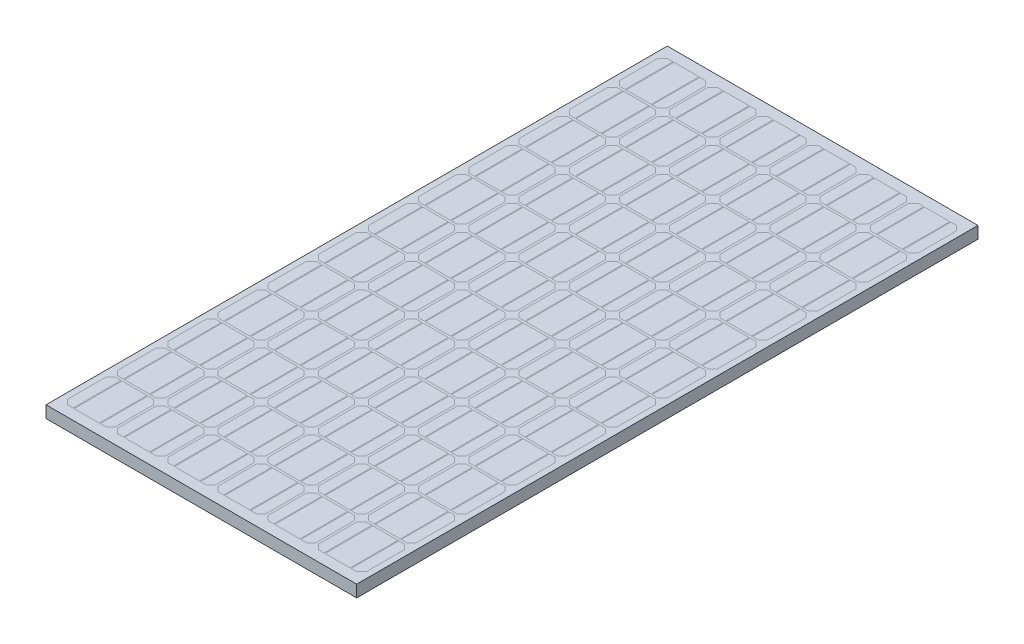
SolidWorks part; units mm, degrees
ref_plane "Front Plane" through (0, 0, 0) normal (0, 0, 1) x (1, 0, 0)
ref_plane "Top Plane" through (0, 0, 0) normal (0, 1, 0) x (1, 0, 0)
ref_plane "Right Plane" through (0, 0, 0) normal (1, 0, 0) x (0, 0, -1)
sketch "Sketch1" plane through (0, 0, 0) normal (0, 1, 0) x (1, 0, 0)
  line L1 (495.3, -990.6) -> (-495.3, -990.6)
  line L2 (495.3, -990.6) -> (495.3, 990.6)
  line L3 (495.3, 990.6) -> (-495.3, 990.6)
  line L4 (-495.3, -990.6) -> (-495.3, 990.6)
  line L5 (495.3, -990.6) -> (-495.3, 990.6) construction
  line L6 (495.3, 990.6) -> (-495.3, -990.6) construction
  point P0 (0, 0)
  dimension "D1" = 1981.2
  dimension "D2" = 990.6
extrude "Boss-Extrude1" add sketch "Sketch1" along normal blind 38.1
sketch "Sketch2" plane through (0, 38.1, 0) normal (0, 1, 0) x (1, 0, 0)
  line L0 (-495.3, 990.6) -> (-495.3, -990.6) construction
  line L1 (-461.2, 956.2) -> (-443, 956.2)
  line L2 (-476.2, 941.2) -> (-476.2, 818.8)
  line L3 (-461.2, 803.8) -> (-443, 803.8)
  line L4 (-323.8, 941.2) -> (-323.8, 818.8)
  line L5 (-476.2, 956.2) -> (-323.8, 803.8) construction
  line L6 (-476.2, 803.8) -> (-323.8, 956.2) construction
  line L7 (495.3, 990.6) -> (-495.3, 990.6) construction
  line L8 (-476.2, 941.2) -> (-461.2, 956.2)
  line L9 (-338.8, 956.2) -> (-323.8, 941.2)
  line L10 (-476.2, 818.8) -> (-461.2, 803.8)
  line L11 (-338.8, 803.8) -> (-323.8, 818.8)
  line L20 (-301.2, 956.2) -> (-283, 956.2)
  line L21 (-316.2, 941.2) -> (-316.2, 818.8)
  line L30 (-301.2, 803.8) -> (-283, 803.8)
  line L31 (-163.8, 941.2) -> (-163.8, 818.8)
  line L40 (-316.2, 941.2) -> (-301.2, 956.2)
  line L41 (-178.8, 956.2) -> (-163.8, 941.2)
  line L50 (-316.2, 818.8) -> (-301.2, 803.8)
  line L51 (-178.8, 803.8) -> (-163.8, 818.8)
  line L60 (-283, 956.2) -> (-283, 803.8)
  line L61 (-280, 956.2) -> (-280, 803.8)
  line L110 (-200, 956.2) -> (-200, 803.8)
  line L111 (-197, 956.2) -> (-197, 803.8)
  line L112 (-280, 956.2) -> (-200, 956.2)
  line L113 (-197, 956.2) -> (-178.8, 956.2)
  line L114 (-280, 803.8) -> (-200, 803.8)
  line L115 (-197, 803.8) -> (-178.8, 803.8)
  line L116 (-316.2, 956.2) -> (-163.8, 803.8) construction
  line L117 (-316.2, 803.8) -> (-163.8, 956.2) construction
  line L118 (-240, 956.2) -> (-240, 803.8) construction
  line L119 (-141.2, 956.2) -> (-123, 956.2)
  line L120 (-156.2, 941.2) -> (-156.2, 818.8)
  line L121 (-141.2, 803.8) -> (-123, 803.8)
  line L170 (-3.8, 941.2) -> (-3.8, 818.8)
  line L171 (-156.2, 941.2) -> (-141.2, 956.2)
  line L172 (-18.8, 956.2) -> (-3.8, 941.2)
  line L173 (-156.2, 818.8) -> (-141.2, 803.8)
  line L174 (-18.8, 803.8) -> (-3.8, 818.8)
  line L175 (-123, 956.2) -> (-123, 803.8)
  line L176 (-120, 956.2) -> (-120, 803.8)
  line L177 (-40, 956.2) -> (-40, 803.8)
  line L178 (-37, 956.2) -> (-37, 803.8)
  line L179 (-120, 956.2) -> (-40, 956.2)
  line L180 (-37, 956.2) -> (-18.8, 956.2)
  line L181 (-120, 803.8) -> (-40, 803.8)
  line L230 (-37, 803.8) -> (-18.8, 803.8)
  line L231 (-156.2, 956.2) -> (-3.8, 803.8) construction
  line L232 (-156.2, 803.8) -> (-3.8, 956.2) construction
  line L233 (-80, 956.2) -> (-80, 803.8) construction
  line L234 (18.8, 956.2) -> (37, 956.2)
  line L235 (3.8, 941.2) -> (3.8, 818.8)
  line L236 (18.8, 803.8) -> (37, 803.8)
  line L237 (156.2, 941.2) -> (156.2, 818.8)
  line L238 (3.8, 941.2) -> (18.8, 956.2)
  line L239 (141.2, 956.2) -> (156.2, 941.2)
  line L240 (3.8, 818.8) -> (18.8, 803.8)
  line L241 (141.2, 803.8) -> (156.2, 818.8)
  line L290 (37, 956.2) -> (37, 803.8)
  line L291 (40, 956.2) -> (40, 803.8)
  line L292 (120, 956.2) -> (120, 803.8)
  line L293 (123, 956.2) -> (123, 803.8)
  line L294 (40, 956.2) -> (120, 956.2)
  line L295 (123, 956.2) -> (141.2, 956.2)
  line L296 (40, 803.8) -> (120, 803.8)
  line L297 (123, 803.8) -> (141.2, 803.8)
  line L298 (3.8, 956.2) -> (156.2, 803.8) construction
  line L299 (3.8, 803.8) -> (156.2, 956.2) construction
  line L300 (80, 956.2) -> (80, 803.8) construction
  line L301 (178.8, 956.2) -> (197, 956.2)
  line L350 (163.8, 941.2) -> (163.8, 818.8)
  line L351 (178.8, 803.8) -> (197, 803.8)
  line L352 (316.2, 941.2) -> (316.2, 818.8)
  line L353 (163.8, 941.2) -> (178.8, 956.2)
  line L354 (301.2, 956.2) -> (316.2, 941.2)
  line L355 (163.8, 818.8) -> (178.8, 803.8)
  line L356 (301.2, 803.8) -> (316.2, 818.8)
  line L357 (197, 956.2) -> (197, 803.8)
  line L358 (200, 956.2) -> (200, 803.8)
  line L359 (280, 956.2) -> (280, 803.8)
  line L360 (283, 956.2) -> (283, 803.8)
  line L361 (200, 956.2) -> (280, 956.2)
  line L410 (283, 956.2) -> (301.2, 956.2)
  line L411 (200, 803.8) -> (280, 803.8)
  line L412 (283, 803.8) -> (301.2, 803.8)
  line L413 (163.8, 956.2) -> (316.2, 803.8) construction
  line L414 (163.8, 803.8) -> (316.2, 956.2) construction
  line L415 (240, 956.2) -> (240, 803.8) construction
  line L416 (338.8, 956.2) -> (357, 956.2)
  line L417 (323.8, 941.2) -> (323.8, 818.8)
  line L418 (338.8, 803.8) -> (357, 803.8)
  line L419 (476.2, 941.2) -> (476.2, 818.8)
  line L420 (323.8, 941.2) -> (338.8, 956.2)
  line L421 (461.2, 956.2) -> (476.2, 941.2)
  line L470 (323.8, 818.8) -> (338.8, 803.8)
  line L471 (461.2, 803.8) -> (476.2, 818.8)
  line L472 (357, 956.2) -> (357, 803.8)
  line L473 (360, 956.2) -> (360, 803.8)
  line L474 (440, 956.2) -> (440, 803.8)
  line L475 (443, 956.2) -> (443, 803.8)
  line L476 (360, 956.2) -> (440, 956.2)
  line L477 (443, 956.2) -> (461.2, 956.2)
  line L478 (360, 803.8) -> (440, 803.8)
  line L479 (443, 803.8) -> (461.2, 803.8)
  line L480 (323.8, 956.2) -> (476.2, 803.8) construction
  line L481 (323.8, 803.8) -> (476.2, 956.2) construction
  line L530 (400, 956.2) -> (400, 803.8) construction
  line L531 (-461.2, 796.2) -> (-443, 796.2)
  line L532 (-476.2, 781.2) -> (-476.2, 658.8)
  line L533 (-461.2, 643.8) -> (-443, 643.8)
  line L534 (-323.8, 781.2) -> (-323.8, 658.8)
  line L535 (-476.2, 781.2) -> (-461.2, 796.2)
  line L536 (-338.8, 796.2) -> (-323.8, 781.2)
  line L537 (-476.2, 658.8) -> (-461.2, 643.8)
  line L538 (-338.8, 643.8) -> (-323.8, 658.8)
  line L539 (-301.2, 796.2) -> (-283, 796.2)
  line L540 (-316.2, 781.2) -> (-316.2, 658.8)
  line L541 (-301.2, 643.8) -> (-283, 643.8)
  line L590 (-163.8, 781.2) -> (-163.8, 658.8)
  line L591 (-316.2, 781.2) -> (-301.2, 796.2)
  line L592 (-178.8, 796.2) -> (-163.8, 781.2)
  line L593 (-316.2, 658.8) -> (-301.2, 643.8)
  line L594 (-178.8, 643.8) -> (-163.8, 658.8)
  line L595 (-283, 796.2) -> (-283, 643.8)
  line L596 (-280, 796.2) -> (-280, 643.8)
  line L597 (-200, 796.2) -> (-200, 643.8)
  line L598 (-197, 796.2) -> (-197, 643.8)
  line L599 (-280, 796.2) -> (-200, 796.2)
  line L600 (-197, 796.2) -> (-178.8, 796.2)
  line L601 (-280, 643.8) -> (-200, 643.8)
  line L650 (-197, 643.8) -> (-178.8, 643.8)
  line L651 (-141.2, 796.2) -> (-123, 796.2)
  line L652 (-156.2, 781.2) -> (-156.2, 658.8)
  line L653 (-141.2, 643.8) -> (-123, 643.8)
  line L654 (-3.8, 781.2) -> (-3.8, 658.8)
  line L655 (-156.2, 781.2) -> (-141.2, 796.2)
  line L656 (-18.8, 796.2) -> (-3.8, 781.2)
  line L657 (-156.2, 658.8) -> (-141.2, 643.8)
  line L658 (-18.8, 643.8) -> (-3.8, 658.8)
  line L659 (-123, 796.2) -> (-123, 643.8)
  line L660 (-120, 796.2) -> (-120, 643.8)
  line L661 (-40, 796.2) -> (-40, 643.8)
  line L710 (-37, 796.2) -> (-37, 643.8)
  line L711 (-120, 796.2) -> (-40, 796.2)
  line L712 (-37, 796.2) -> (-18.8, 796.2)
  line L713 (-120, 643.8) -> (-40, 643.8)
  line L714 (-37, 643.8) -> (-18.8, 643.8)
  line L715 (18.8, 796.2) -> (37, 796.2)
  line L716 (3.8, 781.2) -> (3.8, 658.8)
  line L717 (18.8, 643.8) -> (37, 643.8)
  line L718 (156.2, 781.2) -> (156.2, 658.8)
  line L719 (3.8, 781.2) -> (18.8, 796.2)
  line L720 (141.2, 796.2) -> (156.2, 781.2)
  line L721 (3.8, 658.8) -> (18.8, 643.8)
  line L722 (-400, 956.2) -> (-400, 803.8) construction
  line L724 (-443, 956.2) -> (-443, 803.8)
  line L726 (-440, 956.2) -> (-440, 803.8)
  line L727 (-360, 956.2) -> (-360, 803.8)
  line L728 (-357, 956.2) -> (-357, 803.8)
  line L729 (-440, 956.2) -> (-360, 956.2)
  line L730 (-357, 956.2) -> (-338.8, 956.2)
  line L731 (-440, 803.8) -> (-360, 803.8)
  line L732 (-357, 803.8) -> (-338.8, 803.8)
  line L733 (141.2, 643.8) -> (156.2, 658.8)
  line L734 (37, 796.2) -> (37, 643.8)
  line L735 (40, 796.2) -> (40, 643.8)
  line L736 (120, 796.2) -> (120, 643.8)
  line L737 (123, 796.2) -> (123, 643.8)
  line L738 (40, 796.2) -> (120, 796.2)
  line L739 (123, 796.2) -> (141.2, 796.2)
  line L740 (40, 643.8) -> (120, 643.8)
  line L741 (123, 643.8) -> (141.2, 643.8)
  line L742 (178.8, 796.2) -> (197, 796.2)
  line L743 (163.8, 781.2) -> (163.8, 658.8)
  line L744 (178.8, 643.8) -> (197, 643.8)
  line L745 (316.2, 781.2) -> (316.2, 658.8)
  line L746 (163.8, 781.2) -> (178.8, 796.2)
  line L747 (301.2, 796.2) -> (316.2, 781.2)
  line L748 (163.8, 658.8) -> (178.8, 643.8)
  line L749 (301.2, 643.8) -> (316.2, 658.8)
  line L750 (197, 796.2) -> (197, 643.8)
  line L751 (200, 796.2) -> (200, 643.8)
  line L752 (280, 796.2) -> (280, 643.8)
  line L753 (283, 796.2) -> (283, 643.8)
  line L754 (200, 796.2) -> (280, 796.2)
  line L755 (283, 796.2) -> (301.2, 796.2)
  line L756 (200, 643.8) -> (280, 643.8)
  line L757 (283, 643.8) -> (301.2, 643.8)
  line L758 (338.8, 796.2) -> (357, 796.2)
  line L759 (323.8, 781.2) -> (323.8, 658.8)
  line L760 (338.8, 643.8) -> (357, 643.8)
  line L761 (476.2, 781.2) -> (476.2, 658.8)
  line L762 (323.8, 781.2) -> (338.8, 796.2)
  line L763 (461.2, 796.2) -> (476.2, 781.2)
  line L764 (323.8, 658.8) -> (338.8, 643.8)
  line L765 (461.2, 643.8) -> (476.2, 658.8)
  line L766 (357, 796.2) -> (357, 643.8)
  line L767 (360, 796.2) -> (360, 643.8)
  line L768 (440, 796.2) -> (440, 643.8)
  line L769 (443, 796.2) -> (443, 643.8)
  line L770 (360, 796.2) -> (440, 796.2)
  line L771 (443, 796.2) -> (461.2, 796.2)
  line L772 (360, 643.8) -> (440, 643.8)
  line L773 (443, 643.8) -> (461.2, 643.8)
  line L774 (-443, 796.2) -> (-443, 643.8)
  line L775 (-440, 796.2) -> (-440, 643.8)
  line L776 (-360, 796.2) -> (-360, 643.8)
  line L777 (-357, 796.2) -> (-357, 643.8)
  line L778 (-440, 796.2) -> (-360, 796.2)
  line L779 (-357, 796.2) -> (-338.8, 796.2)
  line L780 (-440, 643.8) -> (-360, 643.8)
  line L784 (-357, 643.8) -> (-338.8, 643.8)
  line L785 (-476.2, 796.2) -> (-323.8, 643.8) construction
  line L786 (-476.2, 643.8) -> (-323.8, 796.2) construction
  line L787 (-316.2, 796.2) -> (-163.8, 643.8) construction
  line L788 (-316.2, 643.8) -> (-163.8, 796.2) construction
  line L789 (-240, 796.2) -> (-240, 643.8) construction
  line L790 (-156.2, 796.2) -> (-3.8, 643.8) construction
  line L791 (-156.2, 643.8) -> (-3.8, 796.2) construction
  line L797 (-80, 796.2) -> (-80, 643.8) construction
  line L798 (3.8, 796.2) -> (156.2, 643.8) construction
  line L799 (3.8, 643.8) -> (156.2, 796.2) construction
  line L800 (80, 796.2) -> (80, 643.8) construction
  line L801 (163.8, 796.2) -> (316.2, 643.8) construction
  line L802 (163.8, 643.8) -> (316.2, 796.2) construction
  line L803 (240, 796.2) -> (240, 643.8) construction
  line L804 (323.8, 796.2) -> (476.2, 643.8) construction
  line L810 (323.8, 643.8) -> (476.2, 796.2) construction
  line L811 (400, 796.2) -> (400, 643.8) construction
  line L812 (-400, 796.2) -> (-400, 643.8) construction
  line L813 (-461.2, 636.2) -> (-443, 636.2)
  line L814 (-476.2, 621.2) -> (-476.2, 498.8)
  line L815 (-461.2, 483.8) -> (-443, 483.8)
  line L816 (-323.8, 621.2) -> (-323.8, 498.8)
  line L817 (-476.2, 621.2) -> (-461.2, 636.2)
  line L823 (-338.8, 636.2) -> (-323.8, 621.2)
  line L824 (-476.2, 498.8) -> (-461.2, 483.8)
  line L825 (-338.8, 483.8) -> (-323.8, 498.8)
  line L826 (-301.2, 636.2) -> (-283, 636.2)
  line L827 (-316.2, 621.2) -> (-316.2, 498.8)
  line L828 (-301.2, 483.8) -> (-283, 483.8)
  line L829 (-163.8, 621.2) -> (-163.8, 498.8)
  line L830 (-316.2, 621.2) -> (-301.2, 636.2)
  line L836 (-178.8, 636.2) -> (-163.8, 621.2)
  line L837 (-316.2, 498.8) -> (-301.2, 483.8)
  line L838 (-178.8, 483.8) -> (-163.8, 498.8)
  line L839 (-283, 636.2) -> (-283, 483.8)
  line L840 (-280, 636.2) -> (-280, 483.8)
  line L841 (-200, 636.2) -> (-200, 483.8)
  line L842 (-197, 636.2) -> (-197, 483.8)
  line L843 (-280, 636.2) -> (-200, 636.2)
  line L849 (-197, 636.2) -> (-178.8, 636.2)
  line L850 (-280, 483.8) -> (-200, 483.8)
  line L851 (-197, 483.8) -> (-178.8, 483.8)
  line L852 (-141.2, 636.2) -> (-123, 636.2)
  line L853 (-156.2, 621.2) -> (-156.2, 498.8)
  line L854 (-141.2, 483.8) -> (-123, 483.8)
  line L855 (-3.8, 621.2) -> (-3.8, 498.8)
  line L856 (-156.2, 621.2) -> (-141.2, 636.2)
  line L862 (-18.8, 636.2) -> (-3.8, 621.2)
  line L863 (-156.2, 498.8) -> (-141.2, 483.8)
  line L864 (-18.8, 483.8) -> (-3.8, 498.8)
  line L865 (-123, 636.2) -> (-123, 483.8)
  line L866 (-120, 636.2) -> (-120, 483.8)
  line L867 (-40, 636.2) -> (-40, 483.8)
  line L868 (-37, 636.2) -> (-37, 483.8)
  line L869 (-120, 636.2) -> (-40, 636.2)
  line L875 (-37, 636.2) -> (-18.8, 636.2)
  line L876 (-120, 483.8) -> (-40, 483.8)
  line L877 (-37, 483.8) -> (-18.8, 483.8)
  line L878 (18.8, 636.2) -> (37, 636.2)
  line L879 (3.8, 621.2) -> (3.8, 498.8)
  line L880 (18.8, 483.8) -> (37, 483.8)
  line L881 (156.2, 621.2) -> (156.2, 498.8)
  line L882 (3.8, 621.2) -> (18.8, 636.2)
  line L888 (141.2, 636.2) -> (156.2, 621.2)
  line L889 (3.8, 498.8) -> (18.8, 483.8)
  line L890 (141.2, 483.8) -> (156.2, 498.8)
  line L891 (37, 636.2) -> (37, 483.8)
  line L892 (40, 636.2) -> (40, 483.8)
  line L893 (120, 636.2) -> (120, 483.8)
  line L894 (123, 636.2) -> (123, 483.8)
  line L895 (40, 636.2) -> (120, 636.2)
  line L901 (123, 636.2) -> (141.2, 636.2)
  line L902 (40, 483.8) -> (120, 483.8)
  line L903 (123, 483.8) -> (141.2, 483.8)
  line L904 (178.8, 636.2) -> (197, 636.2)
  line L905 (163.8, 621.2) -> (163.8, 498.8)
  line L906 (178.8, 483.8) -> (197, 483.8)
  line L907 (316.2, 621.2) -> (316.2, 498.8)
  line L908 (163.8, 621.2) -> (178.8, 636.2)
  line L914 (301.2, 636.2) -> (316.2, 621.2)
  line L915 (163.8, 498.8) -> (178.8, 483.8)
  line L918 (301.2, 483.8) -> (316.2, 498.8)
  line L919 (197, 636.2) -> (197, 483.8)
  line L922 (200, 636.2) -> (200, 483.8)
  line L923 (280, 636.2) -> (280, 483.8)
  line L926 (283, 636.2) -> (283, 483.8)
  line L927 (200, 636.2) -> (280, 636.2)
  line L930 (283, 636.2) -> (301.2, 636.2)
  line L931 (200, 483.8) -> (280, 483.8)
  line L934 (283, 483.8) -> (301.2, 483.8)
  line L935 (338.8, 636.2) -> (357, 636.2)
  line L938 (323.8, 621.2) -> (323.8, 498.8)
  line L939 (338.8, 483.8) -> (357, 483.8)
  line L942 (476.2, 621.2) -> (476.2, 498.8)
  line L943 (323.8, 621.2) -> (338.8, 636.2)
  line L946 (461.2, 636.2) -> (476.2, 621.2)
  line L947 (323.8, 498.8) -> (338.8, 483.8)
  line L950 (461.2, 483.8) -> (476.2, 498.8)
  line L951 (357, 636.2) -> (357, 483.8)
  line L954 (360, 636.2) -> (360, 483.8)
  line L955 (440, 636.2) -> (440, 483.8)
  line L958 (443, 636.2) -> (443, 483.8)
  line L959 (360, 636.2) -> (440, 636.2)
  line L960 (443, 636.2) -> (461.2, 636.2)
  line L961 (360, 483.8) -> (440, 483.8)
  line L962 (443, 483.8) -> (461.2, 483.8)
  line L963 (-443, 636.2) -> (-443, 483.8)
  line L964 (-440, 636.2) -> (-440, 483.8)
  line L965 (-360, 636.2) -> (-360, 483.8)
  line L966 (-357, 636.2) -> (-357, 483.8)
  line L967 (-440, 636.2) -> (-360, 636.2)
  line L968 (-357, 636.2) -> (-338.8, 636.2)
  line L969 (-440, 483.8) -> (-360, 483.8)
  line L970 (-357, 483.8) -> (-338.8, 483.8)
  line L971 (-476.2, 636.2) -> (-323.8, 483.8) construction
  line L972 (-476.2, 483.8) -> (-323.8, 636.2) construction
  line L973 (-316.2, 636.2) -> (-163.8, 483.8) construction
  line L974 (-316.2, 483.8) -> (-163.8, 636.2) construction
  line L975 (-240, 636.2) -> (-240, 483.8) construction
  line L976 (-156.2, 636.2) -> (-3.8, 483.8) construction
  line L977 (-156.2, 483.8) -> (-3.8, 636.2) construction
  line L978 (-80, 636.2) -> (-80, 483.8) construction
  line L979 (3.8, 636.2) -> (156.2, 483.8) construction
  line L980 (3.8, 483.8) -> (156.2, 636.2) construction
  line L981 (80, 636.2) -> (80, 483.8) construction
  line L982 (163.8, 636.2) -> (316.2, 483.8) construction
  line L983 (163.8, 483.8) -> (316.2, 636.2) construction
  line L984 (240, 636.2) -> (240, 483.8) construction
  line L985 (323.8, 636.2) -> (476.2, 483.8) construction
  line L986 (323.8, 483.8) -> (476.2, 636.2) construction
  line L987 (400, 636.2) -> (400, 483.8) construction
  line L988 (-400, 636.2) -> (-400, 483.8) construction
  line L989 (-461.2, 476.2) -> (-443, 476.2)
  line L990 (-476.2, 461.2) -> (-476.2, 338.8)
  line L991 (-461.2, 323.8) -> (-443, 323.8)
  line L992 (-323.8, 461.2) -> (-323.8, 338.8)
  line L993 (-476.2, 461.2) -> (-461.2, 476.2)
  line L994 (-338.8, 476.2) -> (-323.8, 461.2)
  line L995 (-476.2, 338.8) -> (-461.2, 323.8)
  line L996 (-338.8, 323.8) -> (-323.8, 338.8)
  line L997 (-301.2, 476.2) -> (-283, 476.2)
  line L998 (-316.2, 461.2) -> (-316.2, 338.8)
  line L999 (-301.2, 323.8) -> (-283, 323.8)
  line L1000 (-163.8, 461.2) -> (-163.8, 338.8)
  line L1001 (-316.2, 461.2) -> (-301.2, 476.2)
  line L1002 (-178.8, 476.2) -> (-163.8, 461.2)
  line L1003 (-316.2, 338.8) -> (-301.2, 323.8)
  line L1004 (-178.8, 323.8) -> (-163.8, 338.8)
  line L1005 (-283, 476.2) -> (-283, 323.8)
  line L1006 (-280, 476.2) -> (-280, 323.8)
  line L1007 (-200, 476.2) -> (-200, 323.8)
  line L1008 (-197, 476.2) -> (-197, 323.8)
  line L1009 (-280, 476.2) -> (-200, 476.2)
  line L1010 (-197, 476.2) -> (-178.8, 476.2)
  line L1011 (-280, 323.8) -> (-200, 323.8)
  line L1012 (-197, 323.8) -> (-178.8, 323.8)
  line L1013 (-141.2, 476.2) -> (-123, 476.2)
  line L1014 (-156.2, 461.2) -> (-156.2, 338.8)
  line L1015 (-141.2, 323.8) -> (-123, 323.8)
  line L1016 (-3.8, 461.2) -> (-3.8, 338.8)
  line L1017 (-156.2, 461.2) -> (-141.2, 476.2)
  line L1018 (-18.8, 476.2) -> (-3.8, 461.2)
  line L1019 (-156.2, 338.8) -> (-141.2, 323.8)
  line L1020 (-18.8, 323.8) -> (-3.8, 338.8)
  line L1021 (-123, 476.2) -> (-123, 323.8)
  line L1022 (-120, 476.2) -> (-120, 323.8)
  line L1023 (-40, 476.2) -> (-40, 323.8)
  line L1024 (-37, 476.2) -> (-37, 323.8)
  line L1025 (-120, 476.2) -> (-40, 476.2)
  line L1026 (-37, 476.2) -> (-18.8, 476.2)
  line L1027 (-120, 323.8) -> (-40, 323.8)
  line L1028 (-37, 323.8) -> (-18.8, 323.8)
  line L1029 (18.8, 476.2) -> (37, 476.2)
  line L1030 (3.8, 461.2) -> (3.8, 338.8)
  line L1031 (18.8, 323.8) -> (37, 323.8)
  line L1032 (156.2, 461.2) -> (156.2, 338.8)
  line L1033 (3.8, 461.2) -> (18.8, 476.2)
  line L1034 (141.2, 476.2) -> (156.2, 461.2)
  line L1035 (3.8, 338.8) -> (18.8, 323.8)
  line L1036 (141.2, 323.8) -> (156.2, 338.8)
  line L1037 (37, 476.2) -> (37, 323.8)
  line L1038 (40, 476.2) -> (40, 323.8)
  line L1039 (120, 476.2) -> (120, 323.8)
  line L1040 (123, 476.2) -> (123, 323.8)
  line L1041 (40, 476.2) -> (120, 476.2)
  line L1042 (123, 476.2) -> (141.2, 476.2)
  line L1043 (40, 323.8) -> (120, 323.8)
  line L1044 (123, 323.8) -> (141.2, 323.8)
  line L1045 (178.8, 476.2) -> (197, 476.2)
  line L1046 (163.8, 461.2) -> (163.8, 338.8)
  line L1047 (178.8, 323.8) -> (197, 323.8)
  line L1048 (316.2, 461.2) -> (316.2, 338.8)
  line L1049 (163.8, 461.2) -> (178.8, 476.2)
  line L1050 (301.2, 476.2) -> (316.2, 461.2)
  line L1051 (163.8, 338.8) -> (178.8, 323.8)
  line L1052 (301.2, 323.8) -> (316.2, 338.8)
  line L1053 (197, 476.2) -> (197, 323.8)
  line L1054 (200, 476.2) -> (200, 323.8)
  line L1055 (280, 476.2) -> (280, 323.8)
  line L1056 (283, 476.2) -> (283, 323.8)
  line L1057 (200, 476.2) -> (280, 476.2)
  line L1058 (283, 476.2) -> (301.2, 476.2)
  line L1059 (200, 323.8) -> (280, 323.8)
  line L1060 (283, 323.8) -> (301.2, 323.8)
  line L1061 (338.8, 476.2) -> (357, 476.2)
  line L1062 (323.8, 461.2) -> (323.8, 338.8)
  line L1063 (338.8, 323.8) -> (357, 323.8)
  line L1064 (476.2, 461.2) -> (476.2, 338.8)
  line L1065 (323.8, 461.2) -> (338.8, 476.2)
  line L1066 (461.2, 476.2) -> (476.2, 461.2)
  line L1067 (323.8, 338.8) -> (338.8, 323.8)
  line L1068 (461.2, 323.8) -> (476.2, 338.8)
  line L1069 (357, 476.2) -> (357, 323.8)
  line L1070 (360, 476.2) -> (360, 323.8)
  line L1071 (440, 476.2) -> (440, 323.8)
  line L1072 (443, 476.2) -> (443, 323.8)
  line L1073 (360, 476.2) -> (440, 476.2)
  line L1074 (443, 476.2) -> (461.2, 476.2)
  line L1075 (360, 323.8) -> (440, 323.8)
  line L1076 (443, 323.8) -> (461.2, 323.8)
  line L1077 (-443, 476.2) -> (-443, 323.8)
  line L1078 (-440, 476.2) -> (-440, 323.8)
  line L1079 (-360, 476.2) -> (-360, 323.8)
  line L1080 (-357, 476.2) -> (-357, 323.8)
  line L1081 (-440, 476.2) -> (-360, 476.2)
  line L1082 (-357, 476.2) -> (-338.8, 476.2)
  line L1083 (-440, 323.8) -> (-360, 323.8)
  line L1084 (-357, 323.8) -> (-338.8, 323.8)
  line L1085 (-476.2, 476.2) -> (-323.8, 323.8) construction
  line L1086 (-476.2, 323.8) -> (-323.8, 476.2) construction
  line L1087 (-316.2, 476.2) -> (-163.8, 323.8) construction
  line L1088 (-316.2, 323.8) -> (-163.8, 476.2) construction
  line L1089 (-240, 476.2) -> (-240, 323.8) construction
  line L1090 (-156.2, 476.2) -> (-3.8, 323.8) construction
  line L1091 (-156.2, 323.8) -> (-3.8, 476.2) construction
  line L1092 (-80, 476.2) -> (-80, 323.8) construction
  line L1093 (3.8, 476.2) -> (156.2, 323.8) construction
  line L1094 (3.8, 323.8) -> (156.2, 476.2) construction
  line L1095 (80, 476.2) -> (80, 323.8) construction
  line L1096 (163.8, 476.2) -> (316.2, 323.8) construction
  line L1097 (163.8, 323.8) -> (316.2, 476.2) construction
  line L1098 (240, 476.2) -> (240, 323.8) construction
  line L1099 (323.8, 476.2) -> (476.2, 323.8) construction
  line L1100 (323.8, 323.8) -> (476.2, 476.2) construction
  line L1101 (400, 476.2) -> (400, 323.8) construction
  line L1102 (-400, 476.2) -> (-400, 323.8) construction
  line L1103 (-461.2, 316.2) -> (-443, 316.2)
  line L1104 (-476.2, 301.2) -> (-476.2, 178.8)
  line L1105 (-461.2, 163.8) -> (-443, 163.8)
  line L1106 (-323.8, 301.2) -> (-323.8, 178.8)
  line L1107 (-476.2, 301.2) -> (-461.2, 316.2)
  line L1108 (-338.8, 316.2) -> (-323.8, 301.2)
  line L1109 (-476.2, 178.8) -> (-461.2, 163.8)
  line L1110 (-338.8, 163.8) -> (-323.8, 178.8)
  line L1111 (-301.2, 316.2) -> (-283, 316.2)
  line L1112 (-316.2, 301.2) -> (-316.2, 178.8)
  line L1113 (-301.2, 163.8) -> (-283, 163.8)
  line L1114 (-163.8, 301.2) -> (-163.8, 178.8)
  line L1115 (-316.2, 301.2) -> (-301.2, 316.2)
  line L1116 (-178.8, 316.2) -> (-163.8, 301.2)
  line L1117 (-316.2, 178.8) -> (-301.2, 163.8)
  line L1118 (-178.8, 163.8) -> (-163.8, 178.8)
  line L1119 (-283, 316.2) -> (-283, 163.8)
  line L1120 (-280, 316.2) -> (-280, 163.8)
  line L1121 (-200, 316.2) -> (-200, 163.8)
  line L1122 (-197, 316.2) -> (-197, 163.8)
  line L1123 (-280, 316.2) -> (-200, 316.2)
  line L1124 (-197, 316.2) -> (-178.8, 316.2)
  line L1125 (-280, 163.8) -> (-200, 163.8)
  line L1126 (-197, 163.8) -> (-178.8, 163.8)
  line L1127 (-141.2, 316.2) -> (-123, 316.2)
  line L1128 (-156.2, 301.2) -> (-156.2, 178.8)
  line L1129 (-141.2, 163.8) -> (-123, 163.8)
  line L1130 (-3.8, 301.2) -> (-3.8, 178.8)
  line L1131 (-156.2, 301.2) -> (-141.2, 316.2)
  line L1132 (-18.8, 316.2) -> (-3.8, 301.2)
  line L1133 (-156.2, 178.8) -> (-141.2, 163.8)
  line L1134 (-18.8, 163.8) -> (-3.8, 178.8)
  line L1135 (-123, 316.2) -> (-123, 163.8)
  line L1136 (-120, 316.2) -> (-120, 163.8)
  line L1137 (-40, 316.2) -> (-40, 163.8)
  line L1138 (-37, 316.2) -> (-37, 163.8)
  line L1139 (-120, 316.2) -> (-40, 316.2)
  line L1140 (-37, 316.2) -> (-18.8, 316.2)
  line L1141 (-120, 163.8) -> (-40, 163.8)
  line L1142 (-37, 163.8) -> (-18.8, 163.8)
  line L1143 (18.8, 316.2) -> (37, 316.2)
  line L1144 (3.8, 301.2) -> (3.8, 178.8)
  line L1145 (18.8, 163.8) -> (37, 163.8)
  line L1146 (156.2, 301.2) -> (156.2, 178.8)
  line L1147 (3.8, 301.2) -> (18.8, 316.2)
  line L1148 (141.2, 316.2) -> (156.2, 301.2)
  line L1149 (3.8, 178.8) -> (18.8, 163.8)
  line L1150 (141.2, 163.8) -> (156.2, 178.8)
  line L1151 (37, 316.2) -> (37, 163.8)
  line L1152 (40, 316.2) -> (40, 163.8)
  line L1153 (120, 316.2) -> (120, 163.8)
  line L1154 (123, 316.2) -> (123, 163.8)
  line L1155 (40, 316.2) -> (120, 316.2)
  line L1156 (123, 316.2) -> (141.2, 316.2)
  line L1157 (40, 163.8) -> (120, 163.8)
  line L1158 (123, 163.8) -> (141.2, 163.8)
  line L1159 (178.8, 316.2) -> (197, 316.2)
  line L1160 (163.8, 301.2) -> (163.8, 178.8)
  line L1161 (178.8, 163.8) -> (197, 163.8)
  line L1162 (316.2, 301.2) -> (316.2, 178.8)
  line L1163 (163.8, 301.2) -> (178.8, 316.2)
  line L1164 (301.2, 316.2) -> (316.2, 301.2)
  line L1165 (163.8, 178.8) -> (178.8, 163.8)
  line L1166 (301.2, 163.8) -> (316.2, 178.8)
  line L1167 (197, 316.2) -> (197, 163.8)
  line L1168 (200, 316.2) -> (200, 163.8)
  line L1169 (280, 316.2) -> (280, 163.8)
  line L1170 (283, 316.2) -> (283, 163.8)
  line L1171 (200, 316.2) -> (280, 316.2)
  line L1172 (283, 316.2) -> (301.2, 316.2)
  line L1173 (200, 163.8) -> (280, 163.8)
  line L1174 (283, 163.8) -> (301.2, 163.8)
  line L1175 (338.8, 316.2) -> (357, 316.2)
  line L1176 (323.8, 301.2) -> (323.8, 178.8)
  line L1177 (338.8, 163.8) -> (357, 163.8)
  line L1178 (476.2, 301.2) -> (476.2, 178.8)
  line L1179 (323.8, 301.2) -> (338.8, 316.2)
  line L1180 (461.2, 316.2) -> (476.2, 301.2)
  line L1181 (323.8, 178.8) -> (338.8, 163.8)
  line L1182 (461.2, 163.8) -> (476.2, 178.8)
  line L1183 (357, 316.2) -> (357, 163.8)
  line L1184 (360, 316.2) -> (360, 163.8)
  line L1185 (440, 316.2) -> (440, 163.8)
  line L1186 (443, 316.2) -> (443, 163.8)
  line L1187 (360, 316.2) -> (440, 316.2)
  line L1188 (443, 316.2) -> (461.2, 316.2)
  line L1189 (360, 163.8) -> (440, 163.8)
  line L1190 (443, 163.8) -> (461.2, 163.8)
  line L1191 (-443, 316.2) -> (-443, 163.8)
  line L1192 (-440, 316.2) -> (-440, 163.8)
  line L1193 (-360, 316.2) -> (-360, 163.8)
  line L1194 (-357, 316.2) -> (-357, 163.8)
  line L1195 (-440, 316.2) -> (-360, 316.2)
  line L1196 (-357, 316.2) -> (-338.8, 316.2)
  line L1197 (-440, 163.8) -> (-360, 163.8)
  line L1198 (-357, 163.8) -> (-338.8, 163.8)
  line L1199 (-476.2, 316.2) -> (-323.8, 163.8) construction
  line L1200 (-476.2, 163.8) -> (-323.8, 316.2) construction
  line L1201 (-316.2, 316.2) -> (-163.8, 163.8) construction
  line L1202 (-316.2, 163.8) -> (-163.8, 316.2) construction
  line L1203 (-240, 316.2) -> (-240, 163.8) construction
  line L1204 (-156.2, 316.2) -> (-3.8, 163.8) construction
  line L1205 (-156.2, 163.8) -> (-3.8, 316.2) construction
  line L1206 (-80, 316.2) -> (-80, 163.8) construction
  line L1207 (3.8, 316.2) -> (156.2, 163.8) construction
  line L1208 (3.8, 163.8) -> (156.2, 316.2) construction
  line L1209 (80, 316.2) -> (80, 163.8) construction
  line L1210 (163.8, 316.2) -> (316.2, 163.8) construction
  line L1211 (163.8, 163.8) -> (316.2, 316.2) construction
  line L1212 (240, 316.2) -> (240, 163.8) construction
  line L1213 (323.8, 316.2) -> (476.2, 163.8) construction
  line L1214 (323.8, 163.8) -> (476.2, 316.2) construction
  line L1215 (400, 316.2) -> (400, 163.8) construction
  line L1216 (-400, 316.2) -> (-400, 163.8) construction
  line L1217 (-461.2, 156.2) -> (-443, 156.2)
  line L1218 (-476.2, 141.2) -> (-476.2, 18.8)
  line L1219 (-461.2, 3.8) -> (-443, 3.8)
  line L1220 (-323.8, 141.2) -> (-323.8, 18.8)
  line L1221 (-476.2, 141.2) -> (-461.2, 156.2)
  line L1222 (-338.8, 156.2) -> (-323.8, 141.2)
  line L1223 (-476.2, 18.8) -> (-461.2, 3.8)
  line L1224 (-338.8, 3.8) -> (-323.8, 18.8)
  line L1225 (-301.2, 156.2) -> (-283, 156.2)
  line L1226 (-316.2, 141.2) -> (-316.2, 18.8)
  line L1227 (-301.2, 3.8) -> (-283, 3.8)
  line L1228 (-163.8, 141.2) -> (-163.8, 18.8)
  line L1229 (-316.2, 141.2) -> (-301.2, 156.2)
  line L1230 (-178.8, 156.2) -> (-163.8, 141.2)
  line L1231 (-316.2, 18.8) -> (-301.2, 3.8)
  line L1232 (-178.8, 3.8) -> (-163.8, 18.8)
  line L1233 (-283, 156.2) -> (-283, 3.8)
  line L1234 (-280, 156.2) -> (-280, 3.8)
  line L1235 (-200, 156.2) -> (-200, 3.8)
  line L1236 (-197, 156.2) -> (-197, 3.8)
  line L1237 (-280, 156.2) -> (-200, 156.2)
  line L1238 (-197, 156.2) -> (-178.8, 156.2)
  line L1239 (-280, 3.8) -> (-200, 3.8)
  line L1240 (-197, 3.8) -> (-178.8, 3.8)
  line L1241 (-141.2, 156.2) -> (-123, 156.2)
  line L1242 (-156.2, 141.2) -> (-156.2, 18.8)
  line L1243 (-141.2, 3.8) -> (-123, 3.8)
  line L1244 (-3.8, 141.2) -> (-3.8, 18.8)
  line L1245 (-156.2, 141.2) -> (-141.2, 156.2)
  line L1246 (-18.8, 156.2) -> (-3.8, 141.2)
  line L1247 (-156.2, 18.8) -> (-141.2, 3.8)
  line L1248 (-18.8, 3.8) -> (-3.8, 18.8)
  line L1249 (-123, 156.2) -> (-123, 3.8)
  line L1250 (-120, 156.2) -> (-120, 3.8)
  line L1251 (-40, 156.2) -> (-40, 3.8)
  line L1252 (-37, 156.2) -> (-37, 3.8)
  line L1253 (-120, 156.2) -> (-40, 156.2)
  line L1254 (-37, 156.2) -> (-18.8, 156.2)
  line L1255 (-120, 3.8) -> (-40, 3.8)
  line L1256 (-37, 3.8) -> (-18.8, 3.8)
  line L1257 (18.8, 156.2) -> (37, 156.2)
  line L1258 (3.8, 141.2) -> (3.8, 18.8)
  line L1259 (18.8, 3.8) -> (37, 3.8)
  line L1260 (156.2, 141.2) -> (156.2, 18.8)
  line L1261 (3.8, 141.2) -> (18.8, 156.2)
  line L1262 (141.2, 156.2) -> (156.2, 141.2)
  line L1263 (3.8, 18.8) -> (18.8, 3.8)
  line L1264 (141.2, 3.8) -> (156.2, 18.8)
  line L1265 (37, 156.2) -> (37, 3.8)
  line L1266 (40, 156.2) -> (40, 3.8)
  line L1267 (120, 156.2) -> (120, 3.8)
  line L1268 (123, 156.2) -> (123, 3.8)
  line L1269 (40, 156.2) -> (120, 156.2)
  line L1270 (123, 156.2) -> (141.2, 156.2)
  line L1271 (40, 3.8) -> (120, 3.8)
  line L1272 (123, 3.8) -> (141.2, 3.8)
  line L1273 (178.8, 156.2) -> (197, 156.2)
  line L1274 (163.8, 141.2) -> (163.8, 18.8)
  line L1275 (178.8, 3.8) -> (197, 3.8)
  line L1276 (316.2, 141.2) -> (316.2, 18.8)
  line L1277 (163.8, 141.2) -> (178.8, 156.2)
  line L1278 (301.2, 156.2) -> (316.2, 141.2)
  line L1279 (163.8, 18.8) -> (178.8, 3.8)
  line L1280 (301.2, 3.8) -> (316.2, 18.8)
  line L1281 (197, 156.2) -> (197, 3.8)
  line L1282 (200, 156.2) -> (200, 3.8)
  line L1283 (280, 156.2) -> (280, 3.8)
  line L1284 (283, 156.2) -> (283, 3.8)
  line L1285 (200, 156.2) -> (280, 156.2)
  line L1286 (283, 156.2) -> (301.2, 156.2)
  line L1287 (200, 3.8) -> (280, 3.8)
  line L1288 (283, 3.8) -> (301.2, 3.8)
  line L1289 (338.8, 156.2) -> (357, 156.2)
  line L1290 (323.8, 141.2) -> (323.8, 18.8)
  line L1291 (338.8, 3.8) -> (357, 3.8)
  line L1292 (476.2, 141.2) -> (476.2, 18.8)
  line L1293 (323.8, 141.2) -> (338.8, 156.2)
  line L1294 (461.2, 156.2) -> (476.2, 141.2)
  line L1295 (323.8, 18.8) -> (338.8, 3.8)
  line L1296 (461.2, 3.8) -> (476.2, 18.8)
  line L1297 (357, 156.2) -> (357, 3.8)
  line L1298 (360, 156.2) -> (360, 3.8)
  line L1299 (440, 156.2) -> (440, 3.8)
  line L1300 (443, 156.2) -> (443, 3.8)
  line L1301 (360, 156.2) -> (440, 156.2)
  line L1302 (443, 156.2) -> (461.2, 156.2)
  line L1303 (360, 3.8) -> (440, 3.8)
  line L1304 (443, 3.8) -> (461.2, 3.8)
  line L1305 (-443, 156.2) -> (-443, 3.8)
  line L1306 (-440, 156.2) -> (-440, 3.8)
  line L1307 (-360, 156.2) -> (-360, 3.8)
  line L1308 (-357, 156.2) -> (-357, 3.8)
  line L1309 (-440, 156.2) -> (-360, 156.2)
  line L1310 (-357, 156.2) -> (-338.8, 156.2)
  line L1311 (-440, 3.8) -> (-360, 3.8)
  line L1312 (-357, 3.8) -> (-338.8, 3.8)
  line L1313 (-476.2, 156.2) -> (-323.8, 3.8) construction
  line L1314 (-476.2, 3.8) -> (-323.8, 156.2) construction
  line L1315 (-316.2, 156.2) -> (-163.8, 3.8) construction
  line L1316 (-316.2, 3.8) -> (-163.8, 156.2) construction
  line L1317 (-240, 156.2) -> (-240, 3.8) construction
  line L1318 (-156.2, 156.2) -> (-3.8, 3.8) construction
  line L1319 (-156.2, 3.8) -> (-3.8, 156.2) construction
  line L1320 (-80, 156.2) -> (-80, 3.8) construction
  line L1321 (3.8, 156.2) -> (156.2, 3.8) construction
  line L1322 (3.8, 3.8) -> (156.2, 156.2) construction
  line L1323 (80, 156.2) -> (80, 3.8) construction
  line L1324 (163.8, 156.2) -> (316.2, 3.8) construction
  line L1325 (163.8, 3.8) -> (316.2, 156.2) construction
  line L1326 (240, 156.2) -> (240, 3.8) construction
  line L1327 (323.8, 156.2) -> (476.2, 3.8) construction
  line L1328 (323.8, 3.8) -> (476.2, 156.2) construction
  line L1329 (400, 156.2) -> (400, 3.8) construction
  line L1330 (-400, 156.2) -> (-400, 3.8) construction
  line L1331 (-461.2, -3.8) -> (-443, -3.8)
  line L1332 (-476.2, -18.8) -> (-476.2, -141.2)
  line L1333 (-461.2, -156.2) -> (-443, -156.2)
  line L1334 (-323.8, -18.8) -> (-323.8, -141.2)
  line L1335 (-476.2, -18.8) -> (-461.2, -3.8)
  line L1336 (-338.8, -3.8) -> (-323.8, -18.8)
  line L1337 (-476.2, -141.2) -> (-461.2, -156.2)
  line L1338 (-338.8, -156.2) -> (-323.8, -141.2)
  line L1339 (-301.2, -3.8) -> (-283, -3.8)
  line L1340 (-316.2, -18.8) -> (-316.2, -141.2)
  line L1341 (-301.2, -156.2) -> (-283, -156.2)
  line L1342 (-163.8, -18.8) -> (-163.8, -141.2)
  line L1343 (-316.2, -18.8) -> (-301.2, -3.8)
  line L1344 (-178.8, -3.8) -> (-163.8, -18.8)
  line L1345 (-316.2, -141.2) -> (-301.2, -156.2)
  line L1346 (-178.8, -156.2) -> (-163.8, -141.2)
  line L1347 (-283, -3.8) -> (-283, -156.2)
  line L1348 (-280, -3.8) -> (-280, -156.2)
  line L1349 (-200, -3.8) -> (-200, -156.2)
  line L1350 (-197, -3.8) -> (-197, -156.2)
  line L1351 (-280, -3.8) -> (-200, -3.8)
  line L1352 (-197, -3.8) -> (-178.8, -3.8)
  line L1353 (-280, -156.2) -> (-200, -156.2)
  line L1354 (-197, -156.2) -> (-178.8, -156.2)
  line L1355 (-141.2, -3.8) -> (-123, -3.8)
  line L1356 (-156.2, -18.8) -> (-156.2, -141.2)
  line L1357 (-141.2, -156.2) -> (-123, -156.2)
  line L1358 (-3.8, -18.8) -> (-3.8, -141.2)
  line L1359 (-156.2, -18.8) -> (-141.2, -3.8)
  line L1360 (-18.8, -3.8) -> (-3.8, -18.8)
  line L1361 (-156.2, -141.2) -> (-141.2, -156.2)
  line L1362 (-18.8, -156.2) -> (-3.8, -141.2)
  line L1363 (-123, -3.8) -> (-123, -156.2)
  line L1364 (-120, -3.8) -> (-120, -156.2)
  line L1365 (-40, -3.8) -> (-40, -156.2)
  line L1366 (-37, -3.8) -> (-37, -156.2)
  line L1367 (-120, -3.8) -> (-40, -3.8)
  line L1368 (-37, -3.8) -> (-18.8, -3.8)
  line L1369 (-120, -156.2) -> (-40, -156.2)
  line L1370 (-37, -156.2) -> (-18.8, -156.2)
  line L1371 (18.8, -3.8) -> (37, -3.8)
  line L1372 (3.8, -18.8) -> (3.8, -141.2)
  line L1373 (18.8, -156.2) -> (37, -156.2)
  line L1374 (156.2, -18.8) -> (156.2, -141.2)
  line L1375 (3.8, -18.8) -> (18.8, -3.8)
  line L1376 (141.2, -3.8) -> (156.2, -18.8)
  line L1377 (3.8, -141.2) -> (18.8, -156.2)
  line L1378 (141.2, -156.2) -> (156.2, -141.2)
  line L1379 (37, -3.8) -> (37, -156.2)
  line L1380 (40, -3.8) -> (40, -156.2)
  line L1381 (120, -3.8) -> (120, -156.2)
  line L1382 (123, -3.8) -> (123, -156.2)
  line L1383 (40, -3.8) -> (120, -3.8)
  line L1384 (123, -3.8) -> (141.2, -3.8)
  line L1385 (40, -156.2) -> (120, -156.2)
  line L1386 (123, -156.2) -> (141.2, -156.2)
  line L1387 (178.8, -3.8) -> (197, -3.8)
  line L1388 (163.8, -18.8) -> (163.8, -141.2)
  line L1389 (178.8, -156.2) -> (197, -156.2)
  line L1390 (316.2, -18.8) -> (316.2, -141.2)
  line L1391 (163.8, -18.8) -> (178.8, -3.8)
  line L1392 (301.2, -3.8) -> (316.2, -18.8)
  line L1393 (163.8, -141.2) -> (178.8, -156.2)
  line L1394 (301.2, -156.2) -> (316.2, -141.2)
  line L1395 (197, -3.8) -> (197, -156.2)
  line L1396 (200, -3.8) -> (200, -156.2)
  line L1397 (280, -3.8) -> (280, -156.2)
  line L1398 (283, -3.8) -> (283, -156.2)
  line L1399 (200, -3.8) -> (280, -3.8)
  line L1400 (283, -3.8) -> (301.2, -3.8)
  line L1401 (200, -156.2) -> (280, -156.2)
  line L1402 (283, -156.2) -> (301.2, -156.2)
  line L1403 (338.8, -3.8) -> (357, -3.8)
  line L1404 (323.8, -18.8) -> (323.8, -141.2)
  line L1405 (338.8, -156.2) -> (357, -156.2)
  line L1406 (476.2, -18.8) -> (476.2, -141.2)
  line L1407 (323.8, -18.8) -> (338.8, -3.8)
  line L1408 (461.2, -3.8) -> (476.2, -18.8)
  line L1409 (323.8, -141.2) -> (338.8, -156.2)
  line L1410 (461.2, -156.2) -> (476.2, -141.2)
  line L1411 (357, -3.8) -> (357, -156.2)
  line L1412 (360, -3.8) -> (360, -156.2)
  line L1413 (440, -3.8) -> (440, -156.2)
  line L1414 (443, -3.8) -> (443, -156.2)
  line L1415 (360, -3.8) -> (440, -3.8)
  line L1416 (443, -3.8) -> (461.2, -3.8)
  line L1417 (360, -156.2) -> (440, -156.2)
  line L1418 (443, -156.2) -> (461.2, -156.2)
  line L1419 (-443, -3.8) -> (-443, -156.2)
  line L1420 (-440, -3.8) -> (-440, -156.2)
  line L1421 (-360, -3.8) -> (-360, -156.2)
  line L1422 (-357, -3.8) -> (-357, -156.2)
  line L1423 (-440, -3.8) -> (-360, -3.8)
  line L1424 (-357, -3.8) -> (-338.8, -3.8)
  line L1425 (-440, -156.2) -> (-360, -156.2)
  line L1426 (-357, -156.2) -> (-338.8, -156.2)
  line L1427 (-476.2, -3.8) -> (-323.8, -156.2) construction
  line L1428 (-476.2, -156.2) -> (-323.8, -3.8) construction
  line L1429 (-316.2, -3.8) -> (-163.8, -156.2) construction
  line L1430 (-316.2, -156.2) -> (-163.8, -3.8) construction
  line L1431 (-240, -3.8) -> (-240, -156.2) construction
  line L1432 (-156.2, -3.8) -> (-3.8, -156.2) construction
  line L1433 (-156.2, -156.2) -> (-3.8, -3.8) construction
  line L1434 (-80, -3.8) -> (-80, -156.2) construction
  line L1435 (3.8, -3.8) -> (156.2, -156.2) construction
  line L1436 (3.8, -156.2) -> (156.2, -3.8) construction
  line L1437 (80, -3.8) -> (80, -156.2) construction
  line L1438 (163.8, -3.8) -> (316.2, -156.2) construction
  line L1439 (163.8, -156.2) -> (316.2, -3.8) construction
  line L1440 (240, -3.8) -> (240, -156.2) construction
  line L1441 (323.8, -3.8) -> (476.2, -156.2) construction
  line L1442 (323.8, -156.2) -> (476.2, -3.8) construction
  line L1443 (400, -3.8) -> (400, -156.2) construction
  line L1444 (-400, -3.8) -> (-400, -156.2) construction
  line L1445 (-461.2, -163.8) -> (-443, -163.8)
  line L1446 (-476.2, -178.8) -> (-476.2, -301.2)
  line L1447 (-461.2, -316.2) -> (-443, -316.2)
  line L1448 (-323.8, -178.8) -> (-323.8, -301.2)
  line L1449 (-476.2, -178.8) -> (-461.2, -163.8)
  line L1450 (-338.8, -163.8) -> (-323.8, -178.8)
  line L1451 (-476.2, -301.2) -> (-461.2, -316.2)
  line L1452 (-338.8, -316.2) -> (-323.8, -301.2)
  line L1453 (-301.2, -163.8) -> (-283, -163.8)
  line L1454 (-316.2, -178.8) -> (-316.2, -301.2)
  line L1455 (-301.2, -316.2) -> (-283, -316.2)
  line L1456 (-163.8, -178.8) -> (-163.8, -301.2)
  line L1457 (-316.2, -178.8) -> (-301.2, -163.8)
  line L1458 (-178.8, -163.8) -> (-163.8, -178.8)
  line L1459 (-316.2, -301.2) -> (-301.2, -316.2)
  line L1460 (-178.8, -316.2) -> (-163.8, -301.2)
  line L1461 (-283, -163.8) -> (-283, -316.2)
  line L1462 (-280, -163.8) -> (-280, -316.2)
  line L1463 (-200, -163.8) -> (-200, -316.2)
  line L1464 (-197, -163.8) -> (-197, -316.2)
  line L1465 (-280, -163.8) -> (-200, -163.8)
  line L1466 (-197, -163.8) -> (-178.8, -163.8)
  line L1467 (-280, -316.2) -> (-200, -316.2)
  line L1468 (-197, -316.2) -> (-178.8, -316.2)
  line L1469 (-141.2, -163.8) -> (-123, -163.8)
  line L1470 (-156.2, -178.8) -> (-156.2, -301.2)
  line L1471 (-141.2, -316.2) -> (-123, -316.2)
  line L1472 (-3.8, -178.8) -> (-3.8, -301.2)
  line L1473 (-156.2, -178.8) -> (-141.2, -163.8)
  line L1474 (-18.8, -163.8) -> (-3.8, -178.8)
  line L1475 (-156.2, -301.2) -> (-141.2, -316.2)
  line L1476 (-18.8, -316.2) -> (-3.8, -301.2)
  line L1477 (-123, -163.8) -> (-123, -316.2)
  line L1478 (-120, -163.8) -> (-120, -316.2)
  line L1479 (-40, -163.8) -> (-40, -316.2)
  line L1480 (-37, -163.8) -> (-37, -316.2)
  line L1481 (-120, -163.8) -> (-40, -163.8)
  line L1482 (-37, -163.8) -> (-18.8, -163.8)
  line L1483 (-120, -316.2) -> (-40, -316.2)
  line L1484 (-37, -316.2) -> (-18.8, -316.2)
  line L1485 (18.8, -163.8) -> (37, -163.8)
  line L1486 (3.8, -178.8) -> (3.8, -301.2)
  line L1487 (18.8, -316.2) -> (37, -316.2)
  line L1488 (156.2, -178.8) -> (156.2, -301.2)
  line L1489 (3.8, -178.8) -> (18.8, -163.8)
  line L1490 (141.2, -163.8) -> (156.2, -178.8)
  line L1491 (3.8, -301.2) -> (18.8, -316.2)
  line L1492 (141.2, -316.2) -> (156.2, -301.2)
  line L1493 (37, -163.8) -> (37, -316.2)
  line L1494 (40, -163.8) -> (40, -316.2)
  line L1495 (120, -163.8) -> (120, -316.2)
  line L1496 (123, -163.8) -> (123, -316.2)
  line L1497 (40, -163.8) -> (120, -163.8)
  line L1498 (123, -163.8) -> (141.2, -163.8)
  line L1499 (40, -316.2) -> (120, -316.2)
  line L1500 (123, -316.2) -> (141.2, -316.2)
  line L1501 (178.8, -163.8) -> (197, -163.8)
  line L1502 (163.8, -178.8) -> (163.8, -301.2)
  line L1503 (178.8, -316.2) -> (197, -316.2)
  line L1504 (316.2, -178.8) -> (316.2, -301.2)
  line L1505 (163.8, -178.8) -> (178.8, -163.8)
  line L1506 (301.2, -163.8) -> (316.2, -178.8)
  line L1507 (163.8, -301.2) -> (178.8, -316.2)
  line L1508 (301.2, -316.2) -> (316.2, -301.2)
  line L1509 (197, -163.8) -> (197, -316.2)
  line L1510 (200, -163.8) -> (200, -316.2)
  line L1511 (280, -163.8) -> (280, -316.2)
  line L1512 (283, -163.8) -> (283, -316.2)
  line L1513 (200, -163.8) -> (280, -163.8)
  line L1514 (283, -163.8) -> (301.2, -163.8)
  line L1515 (200, -316.2) -> (280, -316.2)
  line L1516 (283, -316.2) -> (301.2, -316.2)
  line L1517 (338.8, -163.8) -> (357, -163.8)
  line L1518 (323.8, -178.8) -> (323.8, -301.2)
  line L1519 (338.8, -316.2) -> (357, -316.2)
  line L1520 (476.2, -178.8) -> (476.2, -301.2)
  line L1521 (323.8, -178.8) -> (338.8, -163.8)
  line L1522 (461.2, -163.8) -> (476.2, -178.8)
  line L1523 (323.8, -301.2) -> (338.8, -316.2)
  line L1524 (461.2, -316.2) -> (476.2, -301.2)
  line L1525 (357, -163.8) -> (357, -316.2)
  line L1526 (360, -163.8) -> (360, -316.2)
  line L1527 (440, -163.8) -> (440, -316.2)
  line L1528 (443, -163.8) -> (443, -316.2)
  line L1529 (360, -163.8) -> (440, -163.8)
  line L1530 (443, -163.8) -> (461.2, -163.8)
  line L1531 (360, -316.2) -> (440, -316.2)
  line L1532 (443, -316.2) -> (461.2, -316.2)
  line L1533 (-443, -163.8) -> (-443, -316.2)
  line L1534 (-440, -163.8) -> (-440, -316.2)
  line L1535 (-360, -163.8) -> (-360, -316.2)
  line L1536 (-357, -163.8) -> (-357, -316.2)
  line L1537 (-440, -163.8) -> (-360, -163.8)
  line L1538 (-357, -163.8) -> (-338.8, -163.8)
  line L1539 (-440, -316.2) -> (-360, -316.2)
  line L1540 (-357, -316.2) -> (-338.8, -316.2)
  line L1541 (-476.2, -163.8) -> (-323.8, -316.2) construction
  line L1542 (-476.2, -316.2) -> (-323.8, -163.8) construction
  line L1543 (-316.2, -163.8) -> (-163.8, -316.2) construction
  line L1544 (-316.2, -316.2) -> (-163.8, -163.8) construction
  line L1545 (-240, -163.8) -> (-240, -316.2) construction
  line L1546 (-156.2, -163.8) -> (-3.8, -316.2) construction
  line L1547 (-156.2, -316.2) -> (-3.8, -163.8) construction
  line L1548 (-80, -163.8) -> (-80, -316.2) construction
  line L1549 (3.8, -163.8) -> (156.2, -316.2) construction
  line L1550 (3.8, -316.2) -> (156.2, -163.8) construction
  line L1551 (80, -163.8) -> (80, -316.2) construction
  line L1552 (163.8, -163.8) -> (316.2, -316.2) construction
  line L1553 (163.8, -316.2) -> (316.2, -163.8) construction
  line L1554 (240, -163.8) -> (240, -316.2) construction
  line L1555 (323.8, -163.8) -> (476.2, -316.2) construction
  line L1556 (323.8, -316.2) -> (476.2, -163.8) construction
  line L1557 (400, -163.8) -> (400, -316.2) construction
  line L1558 (-400, -163.8) -> (-400, -316.2) construction
  line L1559 (-461.2, -323.8) -> (-443, -323.8)
  line L1560 (-476.2, -338.8) -> (-476.2, -461.2)
  line L1561 (-461.2, -476.2) -> (-443, -476.2)
  line L1562 (-323.8, -338.8) -> (-323.8, -461.2)
  line L1563 (-476.2, -338.8) -> (-461.2, -323.8)
  line L1564 (-338.8, -323.8) -> (-323.8, -338.8)
  line L1565 (-476.2, -461.2) -> (-461.2, -476.2)
  line L1566 (-338.8, -476.2) -> (-323.8, -461.2)
  line L1567 (-301.2, -323.8) -> (-283, -323.8)
  line L1568 (-316.2, -338.8) -> (-316.2, -461.2)
  line L1569 (-301.2, -476.2) -> (-283, -476.2)
  line L1570 (-163.8, -338.8) -> (-163.8, -461.2)
  line L1571 (-316.2, -338.8) -> (-301.2, -323.8)
  line L1572 (-178.8, -323.8) -> (-163.8, -338.8)
  line L1573 (-316.2, -461.2) -> (-301.2, -476.2)
  line L1574 (-178.8, -476.2) -> (-163.8, -461.2)
  line L1575 (-283, -323.8) -> (-283, -476.2)
  line L1576 (-280, -323.8) -> (-280, -476.2)
  line L1577 (-200, -323.8) -> (-200, -476.2)
  line L1578 (-197, -323.8) -> (-197, -476.2)
  line L1579 (-280, -323.8) -> (-200, -323.8)
  line L1580 (-197, -323.8) -> (-178.8, -323.8)
  line L1581 (-280, -476.2) -> (-200, -476.2)
  line L1582 (-197, -476.2) -> (-178.8, -476.2)
  line L1583 (-141.2, -323.8) -> (-123, -323.8)
  line L1584 (-156.2, -338.8) -> (-156.2, -461.2)
  line L1585 (-141.2, -476.2) -> (-123, -476.2)
  line L1586 (-3.8, -338.8) -> (-3.8, -461.2)
  line L1587 (-156.2, -338.8) -> (-141.2, -323.8)
  line L1588 (-18.8, -323.8) -> (-3.8, -338.8)
  line L1589 (-156.2, -461.2) -> (-141.2, -476.2)
  line L1590 (-18.8, -476.2) -> (-3.8, -461.2)
  line L1591 (-123, -323.8) -> (-123, -476.2)
  line L1592 (-120, -323.8) -> (-120, -476.2)
  line L1593 (-40, -323.8) -> (-40, -476.2)
  line L1594 (-37, -323.8) -> (-37, -476.2)
  line L1595 (-120, -323.8) -> (-40, -323.8)
  line L1596 (-37, -323.8) -> (-18.8, -323.8)
  line L1597 (-120, -476.2) -> (-40, -476.2)
  line L1598 (-37, -476.2) -> (-18.8, -476.2)
  line L1599 (18.8, -323.8) -> (37, -323.8)
  line L1600 (3.8, -338.8) -> (3.8, -461.2)
  line L1601 (18.8, -476.2) -> (37, -476.2)
  line L1602 (156.2, -338.8) -> (156.2, -461.2)
  line L1603 (3.8, -338.8) -> (18.8, -323.8)
  line L1604 (141.2, -323.8) -> (156.2, -338.8)
  line L1605 (3.8, -461.2) -> (18.8, -476.2)
  line L1606 (141.2, -476.2) -> (156.2, -461.2)
  line L1607 (37, -323.8) -> (37, -476.2)
  line L1608 (40, -323.8) -> (40, -476.2)
  line L1609 (120, -323.8) -> (120, -476.2)
  line L1610 (123, -323.8) -> (123, -476.2)
  line L1611 (40, -323.8) -> (120, -323.8)
  line L1612 (123, -323.8) -> (141.2, -323.8)
  line L1613 (40, -476.2) -> (120, -476.2)
  line L1614 (123, -476.2) -> (141.2, -476.2)
  line L1615 (178.8, -323.8) -> (197, -323.8)
  line L1616 (163.8, -338.8) -> (163.8, -461.2)
  line L1617 (178.8, -476.2) -> (197, -476.2)
  line L1618 (316.2, -338.8) -> (316.2, -461.2)
  line L1619 (163.8, -338.8) -> (178.8, -323.8)
  line L1620 (301.2, -323.8) -> (316.2, -338.8)
  line L1621 (163.8, -461.2) -> (178.8, -476.2)
  line L1622 (301.2, -476.2) -> (316.2, -461.2)
  line L1623 (197, -323.8) -> (197, -476.2)
  line L1624 (200, -323.8) -> (200, -476.2)
  line L1625 (280, -323.8) -> (280, -476.2)
  line L1626 (283, -323.8) -> (283, -476.2)
  line L1627 (200, -323.8) -> (280, -323.8)
  line L1628 (283, -323.8) -> (301.2, -323.8)
  line L1629 (200, -476.2) -> (280, -476.2)
  line L1630 (283, -476.2) -> (301.2, -476.2)
  line L1631 (338.8, -323.8) -> (357, -323.8)
  line L1632 (323.8, -338.8) -> (323.8, -461.2)
  line L1633 (338.8, -476.2) -> (357, -476.2)
  line L1634 (476.2, -338.8) -> (476.2, -461.2)
  line L1635 (323.8, -338.8) -> (338.8, -323.8)
  line L1636 (461.2, -323.8) -> (476.2, -338.8)
  line L1637 (323.8, -461.2) -> (338.8, -476.2)
  line L1638 (461.2, -476.2) -> (476.2, -461.2)
  line L1639 (357, -323.8) -> (357, -476.2)
  line L1640 (360, -323.8) -> (360, -476.2)
  line L1641 (440, -323.8) -> (440, -476.2)
  line L1642 (443, -323.8) -> (443, -476.2)
  line L1643 (360, -323.8) -> (440, -323.8)
  line L1644 (443, -323.8) -> (461.2, -323.8)
  line L1645 (360, -476.2) -> (440, -476.2)
  line L1646 (443, -476.2) -> (461.2, -476.2)
  line L1647 (-443, -323.8) -> (-443, -476.2)
  line L1648 (-440, -323.8) -> (-440, -476.2)
  line L1649 (-360, -323.8) -> (-360, -476.2)
  line L1650 (-357, -323.8) -> (-357, -476.2)
  line L1651 (-440, -323.8) -> (-360, -323.8)
  line L1652 (-357, -323.8) -> (-338.8, -323.8)
  line L1653 (-440, -476.2) -> (-360, -476.2)
  line L1654 (-357, -476.2) -> (-338.8, -476.2)
  line L1655 (-476.2, -323.8) -> (-323.8, -476.2) construction
  line L1656 (-476.2, -476.2) -> (-323.8, -323.8) construction
  line L1657 (-316.2, -323.8) -> (-163.8, -476.2) construction
  line L1658 (-316.2, -476.2) -> (-163.8, -323.8) construction
  line L1659 (-240, -323.8) -> (-240, -476.2) construction
  line L1660 (-156.2, -323.8) -> (-3.8, -476.2) construction
  line L1661 (-156.2, -476.2) -> (-3.8, -323.8) construction
  line L1662 (-80, -323.8) -> (-80, -476.2) construction
  line L1663 (3.8, -323.8) -> (156.2, -476.2) construction
  line L1664 (3.8, -476.2) -> (156.2, -323.8) construction
  line L1665 (80, -323.8) -> (80, -476.2) construction
  line L1666 (163.8, -323.8) -> (316.2, -476.2) construction
  line L1667 (163.8, -476.2) -> (316.2, -323.8) construction
  line L1668 (240, -323.8) -> (240, -476.2) construction
  line L1669 (323.8, -323.8) -> (476.2, -476.2) construction
  line L1670 (323.8, -476.2) -> (476.2, -323.8) construction
  line L1671 (400, -323.8) -> (400, -476.2) construction
  line L1672 (-400, -323.8) -> (-400, -476.2) construction
  line L1673 (-461.2, -483.8) -> (-443, -483.8)
  line L1674 (-476.2, -498.8) -> (-476.2, -621.2)
  line L1675 (-461.2, -636.2) -> (-443, -636.2)
  line L1676 (-323.8, -498.8) -> (-323.8, -621.2)
  line L1677 (-476.2, -498.8) -> (-461.2, -483.8)
  line L1678 (-338.8, -483.8) -> (-323.8, -498.8)
  line L1679 (-476.2, -621.2) -> (-461.2, -636.2)
  line L1680 (-338.8, -636.2) -> (-323.8, -621.2)
  line L1681 (-301.2, -483.8) -> (-283, -483.8)
  line L1682 (-316.2, -498.8) -> (-316.2, -621.2)
  line L1683 (-301.2, -636.2) -> (-283, -636.2)
  line L1684 (-163.8, -498.8) -> (-163.8, -621.2)
  line L1685 (-316.2, -498.8) -> (-301.2, -483.8)
  line L1686 (-178.8, -483.8) -> (-163.8, -498.8)
  line L1687 (-316.2, -621.2) -> (-301.2, -636.2)
  line L1688 (-178.8, -636.2) -> (-163.8, -621.2)
  line L1689 (-283, -483.8) -> (-283, -636.2)
  line L1690 (-280, -483.8) -> (-280, -636.2)
  line L1691 (-200, -483.8) -> (-200, -636.2)
  line L1692 (-197, -483.8) -> (-197, -636.2)
  line L1693 (-280, -483.8) -> (-200, -483.8)
  line L1694 (-197, -483.8) -> (-178.8, -483.8)
  line L1695 (-280, -636.2) -> (-200, -636.2)
  line L1696 (-197, -636.2) -> (-178.8, -636.2)
  line L1697 (-141.2, -483.8) -> (-123, -483.8)
  line L1698 (-156.2, -498.8) -> (-156.2, -621.2)
  line L1699 (-141.2, -636.2) -> (-123, -636.2)
  line L1700 (-3.8, -498.8) -> (-3.8, -621.2)
  line L1701 (-156.2, -498.8) -> (-141.2, -483.8)
  line L1702 (-18.8, -483.8) -> (-3.8, -498.8)
  line L1703 (-156.2, -621.2) -> (-141.2, -636.2)
  line L1704 (-18.8, -636.2) -> (-3.8, -621.2)
  line L1705 (-123, -483.8) -> (-123, -636.2)
  line L1706 (-120, -483.8) -> (-120, -636.2)
  line L1707 (-40, -483.8) -> (-40, -636.2)
  line L1708 (-37, -483.8) -> (-37, -636.2)
  line L1709 (-120, -483.8) -> (-40, -483.8)
  line L1710 (-37, -483.8) -> (-18.8, -483.8)
  line L1711 (-120, -636.2) -> (-40, -636.2)
  line L1712 (-37, -636.2) -> (-18.8, -636.2)
  line L1713 (18.8, -483.8) -> (37, -483.8)
  line L1714 (3.8, -498.8) -> (3.8, -621.2)
  line L1715 (18.8, -636.2) -> (37, -636.2)
  line L1716 (156.2, -498.8) -> (156.2, -621.2)
  line L1717 (3.8, -498.8) -> (18.8, -483.8)
  line L1718 (141.2, -483.8) -> (156.2, -498.8)
  line L1719 (3.8, -621.2) -> (18.8, -636.2)
  line L1720 (141.2, -636.2) -> (156.2, -621.2)
  line L1721 (37, -483.8) -> (37, -636.2)
  line L1722 (40, -483.8) -> (40, -636.2)
  line L1723 (120, -483.8) -> (120, -636.2)
  line L1724 (123, -483.8) -> (123, -636.2)
  line L1725 (40, -483.8) -> (120, -483.8)
  line L1726 (123, -483.8) -> (141.2, -483.8)
  line L1727 (40, -636.2) -> (120, -636.2)
  line L1728 (123, -636.2) -> (141.2, -636.2)
  line L1729 (178.8, -483.8) -> (197, -483.8)
  line L1730 (163.8, -498.8) -> (163.8, -621.2)
  line L1731 (178.8, -636.2) -> (197, -636.2)
  line L1732 (316.2, -498.8) -> (316.2, -621.2)
  line L1733 (163.8, -498.8) -> (178.8, -483.8)
  line L1734 (301.2, -483.8) -> (316.2, -498.8)
  line L1735 (163.8, -621.2) -> (178.8, -636.2)
  line L1736 (301.2, -636.2) -> (316.2, -621.2)
  line L1737 (197, -483.8) -> (197, -636.2)
  line L1738 (200, -483.8) -> (200, -636.2)
  line L1739 (280, -483.8) -> (280, -636.2)
  line L1740 (283, -483.8) -> (283, -636.2)
  line L1741 (200, -483.8) -> (280, -483.8)
  line L1742 (283, -483.8) -> (301.2, -483.8)
  line L1743 (200, -636.2) -> (280, -636.2)
  line L1744 (283, -636.2) -> (301.2, -636.2)
  line L1745 (338.8, -483.8) -> (357, -483.8)
  line L1746 (323.8, -498.8) -> (323.8, -621.2)
  line L1747 (338.8, -636.2) -> (357, -636.2)
  line L1748 (476.2, -498.8) -> (476.2, -621.2)
  line L1749 (323.8, -498.8) -> (338.8, -483.8)
  line L1750 (461.2, -483.8) -> (476.2, -498.8)
  line L1751 (323.8, -621.2) -> (338.8, -636.2)
  line L1752 (461.2, -636.2) -> (476.2, -621.2)
  line L1753 (357, -483.8) -> (357, -636.2)
  line L1754 (360, -483.8) -> (360, -636.2)
  line L1755 (440, -483.8) -> (440, -636.2)
  line L1756 (443, -483.8) -> (443, -636.2)
  line L1757 (360, -483.8) -> (440, -483.8)
  line L1758 (443, -483.8) -> (461.2, -483.8)
  line L1759 (360, -636.2) -> (440, -636.2)
  line L1760 (443, -636.2) -> (461.2, -636.2)
  line L1761 (-443, -483.8) -> (-443, -636.2)
  line L1762 (-440, -483.8) -> (-440, -636.2)
  line L1763 (-360, -483.8) -> (-360, -636.2)
  line L1764 (-357, -483.8) -> (-357, -636.2)
  line L1765 (-440, -483.8) -> (-360, -483.8)
  line L1766 (-357, -483.8) -> (-338.8, -483.8)
  line L1767 (-440, -636.2) -> (-360, -636.2)
  line L1768 (-357, -636.2) -> (-338.8, -636.2)
  line L1769 (-476.2, -483.8) -> (-323.8, -636.2) construction
  line L1770 (-476.2, -636.2) -> (-323.8, -483.8) construction
  line L1771 (-316.2, -483.8) -> (-163.8, -636.2) construction
  line L1772 (-316.2, -636.2) -> (-163.8, -483.8) construction
  line L1773 (-240, -483.8) -> (-240, -636.2) construction
  line L1774 (-156.2, -483.8) -> (-3.8, -636.2) construction
  line L1775 (-156.2, -636.2) -> (-3.8, -483.8) construction
  line L1776 (-80, -483.8) -> (-80, -636.2) construction
  line L1777 (3.8, -483.8) -> (156.2, -636.2) construction
  line L1778 (3.8, -636.2) -> (156.2, -483.8) construction
  line L1779 (80, -483.8) -> (80, -636.2) construction
  line L1780 (163.8, -483.8) -> (316.2, -636.2) construction
  line L1781 (163.8, -636.2) -> (316.2, -483.8) construction
  line L1782 (240, -483.8) -> (240, -636.2) construction
  line L1783 (323.8, -483.8) -> (476.2, -636.2) construction
  line L1784 (323.8, -636.2) -> (476.2, -483.8) construction
  line L1785 (400, -483.8) -> (400, -636.2) construction
  line L1786 (-400, -483.8) -> (-400, -636.2) construction
  line L1787 (-461.2, -643.8) -> (-443, -643.8)
  line L1788 (-476.2, -658.8) -> (-476.2, -781.2)
  line L1789 (-461.2, -796.2) -> (-443, -796.2)
  line L1790 (-323.8, -658.8) -> (-323.8, -781.2)
  line L1791 (-476.2, -658.8) -> (-461.2, -643.8)
  line L1792 (-338.8, -643.8) -> (-323.8, -658.8)
  line L1793 (-476.2, -781.2) -> (-461.2, -796.2)
  line L1794 (-338.8, -796.2) -> (-323.8, -781.2)
  line L1795 (-301.2, -643.8) -> (-283, -643.8)
  line L1796 (-316.2, -658.8) -> (-316.2, -781.2)
  line L1797 (-301.2, -796.2) -> (-283, -796.2)
  line L1798 (-163.8, -658.8) -> (-163.8, -781.2)
  line L1799 (-316.2, -658.8) -> (-301.2, -643.8)
  line L1800 (-178.8, -643.8) -> (-163.8, -658.8)
  line L1801 (-316.2, -781.2) -> (-301.2, -796.2)
  line L1802 (-178.8, -796.2) -> (-163.8, -781.2)
  line L1803 (-283, -643.8) -> (-283, -796.2)
  line L1804 (-280, -643.8) -> (-280, -796.2)
  line L1805 (-200, -643.8) -> (-200, -796.2)
  line L1806 (-197, -643.8) -> (-197, -796.2)
  line L1807 (-280, -643.8) -> (-200, -643.8)
  line L1808 (-197, -643.8) -> (-178.8, -643.8)
  line L1809 (-280, -796.2) -> (-200, -796.2)
  line L1810 (-197, -796.2) -> (-178.8, -796.2)
  line L1811 (-141.2, -643.8) -> (-123, -643.8)
  line L1812 (-156.2, -658.8) -> (-156.2, -781.2)
  line L1813 (-141.2, -796.2) -> (-123, -796.2)
  line L1814 (-3.8, -658.8) -> (-3.8, -781.2)
  line L1815 (-156.2, -658.8) -> (-141.2, -643.8)
  line L1816 (-18.8, -643.8) -> (-3.8, -658.8)
  line L1817 (-156.2, -781.2) -> (-141.2, -796.2)
  line L1818 (-18.8, -796.2) -> (-3.8, -781.2)
  line L1819 (-123, -643.8) -> (-123, -796.2)
  line L1820 (-120, -643.8) -> (-120, -796.2)
  line L1821 (-40, -643.8) -> (-40, -796.2)
  line L1822 (-37, -643.8) -> (-37, -796.2)
  line L1823 (-120, -643.8) -> (-40, -643.8)
  line L1824 (-37, -643.8) -> (-18.8, -643.8)
  line L1825 (-120, -796.2) -> (-40, -796.2)
  line L1826 (-37, -796.2) -> (-18.8, -796.2)
  line L1827 (18.8, -643.8) -> (37, -643.8)
  line L1828 (3.8, -658.8) -> (3.8, -781.2)
  line L1829 (18.8, -796.2) -> (37, -796.2)
  line L1830 (156.2, -658.8) -> (156.2, -781.2)
  line L1831 (3.8, -658.8) -> (18.8, -643.8)
  line L1832 (141.2, -643.8) -> (156.2, -658.8)
  line L1833 (3.8, -781.2) -> (18.8, -796.2)
  line L1834 (141.2, -796.2) -> (156.2, -781.2)
  line L1835 (37, -643.8) -> (37, -796.2)
  line L1836 (40, -643.8) -> (40, -796.2)
  line L1837 (120, -643.8) -> (120, -796.2)
  line L1838 (123, -643.8) -> (123, -796.2)
  line L1839 (40, -643.8) -> (120, -643.8)
  line L1840 (123, -643.8) -> (141.2, -643.8)
  line L1841 (40, -796.2) -> (120, -796.2)
  line L1842 (123, -796.2) -> (141.2, -796.2)
  line L1843 (178.8, -643.8) -> (197, -643.8)
  line L1844 (163.8, -658.8) -> (163.8, -781.2)
  line L1845 (178.8, -796.2) -> (197, -796.2)
  line L1846 (316.2, -658.8) -> (316.2, -781.2)
  line L1847 (163.8, -658.8) -> (178.8, -643.8)
  line L1848 (301.2, -643.8) -> (316.2, -658.8)
  line L1849 (163.8, -781.2) -> (178.8, -796.2)
  line L1850 (301.2, -796.2) -> (316.2, -781.2)
  line L1851 (197, -643.8) -> (197, -796.2)
  line L1852 (200, -643.8) -> (200, -796.2)
  line L1853 (280, -643.8) -> (280, -796.2)
  line L1854 (283, -643.8) -> (283, -796.2)
  line L1855 (200, -643.8) -> (280, -643.8)
  line L1856 (283, -643.8) -> (301.2, -643.8)
  line L1857 (200, -796.2) -> (280, -796.2)
  line L1858 (283, -796.2) -> (301.2, -796.2)
  line L1859 (338.8, -643.8) -> (357, -643.8)
  line L1860 (323.8, -658.8) -> (323.8, -781.2)
  line L1861 (338.8, -796.2) -> (357, -796.2)
  line L1862 (476.2, -658.8) -> (476.2, -781.2)
  line L1863 (323.8, -658.8) -> (338.8, -643.8)
  line L1864 (461.2, -643.8) -> (476.2, -658.8)
  line L1865 (323.8, -781.2) -> (338.8, -796.2)
  line L1866 (461.2, -796.2) -> (476.2, -781.2)
  line L1867 (357, -643.8) -> (357, -796.2)
  line L1868 (360, -643.8) -> (360, -796.2)
  line L1869 (440, -643.8) -> (440, -796.2)
  line L1870 (443, -643.8) -> (443, -796.2)
  line L1871 (360, -643.8) -> (440, -643.8)
  line L1872 (443, -643.8) -> (461.2, -643.8)
  line L1873 (360, -796.2) -> (440, -796.2)
  line L1874 (443, -796.2) -> (461.2, -796.2)
  line L1875 (-443, -643.8) -> (-443, -796.2)
  line L1876 (-440, -643.8) -> (-440, -796.2)
  line L1877 (-360, -643.8) -> (-360, -796.2)
  line L1878 (-357, -643.8) -> (-357, -796.2)
  line L1879 (-440, -643.8) -> (-360, -643.8)
  line L1880 (-357, -643.8) -> (-338.8, -643.8)
  line L1881 (-440, -796.2) -> (-360, -796.2)
  line L1882 (-357, -796.2) -> (-338.8, -796.2)
  line L1883 (-476.2, -643.8) -> (-323.8, -796.2) construction
  line L1884 (-476.2, -796.2) -> (-323.8, -643.8) construction
  line L1885 (-316.2, -643.8) -> (-163.8, -796.2) construction
  line L1886 (-316.2, -796.2) -> (-163.8, -643.8) construction
  line L1887 (-240, -643.8) -> (-240, -796.2) construction
  line L1888 (-156.2, -643.8) -> (-3.8, -796.2) construction
  line L1889 (-156.2, -796.2) -> (-3.8, -643.8) construction
  line L1890 (-80, -643.8) -> (-80, -796.2) construction
  line L1891 (3.8, -643.8) -> (156.2, -796.2) construction
  line L1892 (3.8, -796.2) -> (156.2, -643.8) construction
  line L1893 (80, -643.8) -> (80, -796.2) construction
  line L1894 (163.8, -643.8) -> (316.2, -796.2) construction
  line L1895 (163.8, -796.2) -> (316.2, -643.8) construction
  line L1896 (240, -643.8) -> (240, -796.2) construction
  line L1897 (323.8, -643.8) -> (476.2, -796.2) construction
  line L1898 (323.8, -796.2) -> (476.2, -643.8) construction
  line L1899 (400, -643.8) -> (400, -796.2) construction
  line L1900 (-400, -643.8) -> (-400, -796.2) construction
  line L1901 (-461.2, -803.8) -> (-443, -803.8)
  line L1902 (-476.2, -818.8) -> (-476.2, -941.2)
  line L1903 (-461.2, -956.2) -> (-443, -956.2)
  line L1904 (-323.8, -818.8) -> (-323.8, -941.2)
  line L1905 (-476.2, -818.8) -> (-461.2, -803.8)
  line L1906 (-338.8, -803.8) -> (-323.8, -818.8)
  line L1907 (-476.2, -941.2) -> (-461.2, -956.2)
  line L1908 (-338.8, -956.2) -> (-323.8, -941.2)
  line L1909 (-301.2, -803.8) -> (-283, -803.8)
  line L1910 (-316.2, -818.8) -> (-316.2, -941.2)
  line L1911 (-301.2, -956.2) -> (-283, -956.2)
  line L1912 (-163.8, -818.8) -> (-163.8, -941.2)
  line L1913 (-316.2, -818.8) -> (-301.2, -803.8)
  line L1914 (-178.8, -803.8) -> (-163.8, -818.8)
  line L1915 (-316.2, -941.2) -> (-301.2, -956.2)
  line L1916 (-178.8, -956.2) -> (-163.8, -941.2)
  line L1917 (-283, -803.8) -> (-283, -956.2)
  line L1918 (-280, -803.8) -> (-280, -956.2)
  line L1919 (-200, -803.8) -> (-200, -956.2)
  line L1920 (-197, -803.8) -> (-197, -956.2)
  line L1921 (-280, -803.8) -> (-200, -803.8)
  line L1922 (-197, -803.8) -> (-178.8, -803.8)
  line L1923 (-280, -956.2) -> (-200, -956.2)
  line L1924 (-197, -956.2) -> (-178.8, -956.2)
  line L1925 (-141.2, -803.8) -> (-123, -803.8)
  line L1926 (-156.2, -818.8) -> (-156.2, -941.2)
  line L1927 (-141.2, -956.2) -> (-123, -956.2)
  line L1928 (-3.8, -818.8) -> (-3.8, -941.2)
  line L1929 (-156.2, -818.8) -> (-141.2, -803.8)
  line L1930 (-18.8, -803.8) -> (-3.8, -818.8)
  line L1931 (-156.2, -941.2) -> (-141.2, -956.2)
  line L1932 (-18.8, -956.2) -> (-3.8, -941.2)
  line L1933 (-123, -803.8) -> (-123, -956.2)
  line L1934 (-120, -803.8) -> (-120, -956.2)
  line L1935 (-40, -803.8) -> (-40, -956.2)
  line L1936 (-37, -803.8) -> (-37, -956.2)
  line L1937 (-120, -803.8) -> (-40, -803.8)
  line L1938 (-37, -803.8) -> (-18.8, -803.8)
  line L1939 (-120, -956.2) -> (-40, -956.2)
  line L1940 (-37, -956.2) -> (-18.8, -956.2)
  line L1941 (18.8, -803.8) -> (37, -803.8)
  line L1942 (3.8, -818.8) -> (3.8, -941.2)
  line L1943 (18.8, -956.2) -> (37, -956.2)
  line L1944 (156.2, -818.8) -> (156.2, -941.2)
  line L1945 (3.8, -818.8) -> (18.8, -803.8)
  line L1946 (141.2, -803.8) -> (156.2, -818.8)
  line L1947 (3.8, -941.2) -> (18.8, -956.2)
  line L1948 (141.2, -956.2) -> (156.2, -941.2)
  line L1949 (37, -803.8) -> (37, -956.2)
  line L1950 (40, -803.8) -> (40, -956.2)
  line L1951 (120, -803.8) -> (120, -956.2)
  line L1952 (123, -803.8) -> (123, -956.2)
  line L1953 (40, -803.8) -> (120, -803.8)
  line L1954 (123, -803.8) -> (141.2, -803.8)
  line L1955 (40, -956.2) -> (120, -956.2)
  line L1956 (123, -956.2) -> (141.2, -956.2)
  line L1957 (178.8, -803.8) -> (197, -803.8)
  line L1958 (163.8, -818.8) -> (163.8, -941.2)
  line L1959 (178.8, -956.2) -> (197, -956.2)
  line L1960 (316.2, -818.8) -> (316.2, -941.2)
  line L1961 (163.8, -818.8) -> (178.8, -803.8)
  line L1962 (301.2, -803.8) -> (316.2, -818.8)
  line L1963 (163.8, -941.2) -> (178.8, -956.2)
  line L1964 (301.2, -956.2) -> (316.2, -941.2)
  line L1965 (197, -803.8) -> (197, -956.2)
  line L1966 (200, -803.8) -> (200, -956.2)
  line L1967 (280, -803.8) -> (280, -956.2)
  line L1968 (283, -803.8) -> (283, -956.2)
  line L1969 (200, -803.8) -> (280, -803.8)
  line L1970 (283, -803.8) -> (301.2, -803.8)
  line L1971 (200, -956.2) -> (280, -956.2)
  line L1972 (283, -956.2) -> (301.2, -956.2)
  line L1973 (338.8, -803.8) -> (357, -803.8)
  line L1974 (323.8, -818.8) -> (323.8, -941.2)
  line L1975 (338.8, -956.2) -> (357, -956.2)
  line L1976 (476.2, -818.8) -> (476.2, -941.2)
  line L1977 (323.8, -818.8) -> (338.8, -803.8)
  line L1978 (461.2, -803.8) -> (476.2, -818.8)
  line L1979 (323.8, -941.2) -> (338.8, -956.2)
  line L1980 (461.2, -956.2) -> (476.2, -941.2)
  line L1981 (357, -803.8) -> (357, -956.2)
  line L1982 (360, -803.8) -> (360, -956.2)
  line L1983 (440, -803.8) -> (440, -956.2)
  line L1984 (443, -803.8) -> (443, -956.2)
  line L1985 (360, -803.8) -> (440, -803.8)
  line L1986 (443, -803.8) -> (461.2, -803.8)
  line L1987 (360, -956.2) -> (440, -956.2)
  line L1988 (443, -956.2) -> (461.2, -956.2)
  line L1989 (-443, -803.8) -> (-443, -956.2)
  line L1990 (-440, -803.8) -> (-440, -956.2)
  line L1991 (-360, -803.8) -> (-360, -956.2)
  line L1992 (-357, -803.8) -> (-357, -956.2)
  line L1993 (-440, -803.8) -> (-360, -803.8)
  line L1994 (-357, -803.8) -> (-338.8, -803.8)
  line L1995 (-440, -956.2) -> (-360, -956.2)
  line L1996 (-357, -956.2) -> (-338.8, -956.2)
  line L1997 (-476.2, -803.8) -> (-323.8, -956.2) construction
  line L1998 (-476.2, -956.2) -> (-323.8, -803.8) construction
  line L1999 (-316.2, -803.8) -> (-163.8, -956.2) construction
  line L2000 (-316.2, -956.2) -> (-163.8, -803.8) construction
  line L2001 (-240, -803.8) -> (-240, -956.2) construction
  line L2002 (-156.2, -803.8) -> (-3.8, -956.2) construction
  line L2003 (-156.2, -956.2) -> (-3.8, -803.8) construction
  line L2004 (-80, -803.8) -> (-80, -956.2) construction
  line L2005 (3.8, -803.8) -> (156.2, -956.2) construction
  line L2006 (3.8, -956.2) -> (156.2, -803.8) construction
  line L2007 (80, -803.8) -> (80, -956.2) construction
  line L2008 (163.8, -803.8) -> (316.2, -956.2) construction
  line L2009 (163.8, -956.2) -> (316.2, -803.8) construction
  line L2010 (240, -803.8) -> (240, -956.2) construction
  line L2011 (323.8, -803.8) -> (476.2, -956.2) construction
  line L2012 (323.8, -956.2) -> (476.2, -803.8) construction
  line L2013 (400, -803.8) -> (400, -956.2) construction
  line L2014 (-400, -803.8) -> (-400, -956.2) construction
  point P0 (-400, 880)
  point P20 (-240, 880)
  point P27 (400, -880)
  point P31 (240, -880)
  point P32 (-240, -880)
  point P33 (80, -880)
  point P34 (-80, -880)
  point P35 (400, -720)
  point P36 (240, -720)
  point P37 (80, -720)
  point P38 (-80, -720)
  point P39 (400, -560)
  point P40 (240, -560)
  point P41 (80, -560)
  point P42 (-80, -560)
  point P43 (400, -400)
  point P44 (240, -400)
  point P46 (80, -400)
  point P47 (-80, -400)
  point P48 (400, -240)
  point P49 (240, -240)
  point P50 (80, -240)
  point P51 (-80, -240)
  point P52 (400, -80)
  point P53 (240, -80)
  point P54 (80, -80)
  point P55 (-80, -80)
  point P56 (400, 80)
  point P57 (240, 80)
  point P59 (80, 80)
  point P60 (-80, 80)
  point P61 (400, 240)
  point P62 (240, 240)
  point P63 (80, 240)
  point P64 (-80, 240)
  point P65 (400, 400)
  point P66 (240, 400)
  point P67 (80, 400)
  point P68 (-80, 400)
  point P69 (400, 560)
  point P70 (240, 560)
  point P72 (80, 560)
  point P73 (-80, 560)
  point P74 (400, 720)
  point P75 (240, 720)
  point P76 (80, 720)
  point P77 (-80, 720)
  point P80 (-240, -720)
  point P82 (-240, -560)
  point P85 (-240, -400)
  point P87 (-240, -240)
  point P92 (-80, 880)
  point P93 (-240, -80)
  point P95 (-240, 80)
  point P98 (-240, 240)
  point P100 (-240, 400)
  point P105 (-240, 560)
  point P120 (80, 880)
  point P143 (240, 880)
  point P166 (400, 880)
  point P189 (-400, 720)
  point P204 (-240, 720)
  point P227 (-80, 720)
  point P250 (80, 720)
  point P273 (240, 720)
  point P296 (400, 720)
  point P327 (-400, 560)
  point P342 (-240, 560)
  point P365 (-80, 560)
  point P388 (80, 560)
  point P411 (240, 560)
  point P434 (400, 560)
  point P465 (-400, 400)
  point P480 (-240, 400)
  point P503 (-80, 400)
  point P526 (80, 400)
  point P549 (240, 400)
  point P572 (400, 400)
  point P603 (-400, 240)
  point P618 (-240, 240)
  point P641 (-80, 240)
  point P664 (80, 240)
  point P687 (240, 240)
  point P710 (400, 240)
  point P741 (-400, 80)
  point P756 (-240, 80)
  point P779 (-80, 80)
  point P802 (80, 80)
  point P825 (240, 80)
  point P848 (400, 80)
  point P879 (-400, -80)
  point P894 (-240, -80)
  point P917 (-80, -80)
  point P940 (80, -80)
  point P971 (240, -80)
  point P994 (400, -80)
  point P1025 (-400, -240)
  point P1040 (-240, -240)
  point P1079 (-80, -240)
  point P1112 (80, -240)
  point P1145 (240, -240)
  point P1188 (400, -240)
  point P1239 (-400, -400)
  point P1264 (-240, -400)
  point P1297 (-80, -400)
  point P1346 (80, -400)
  point P1393 (240, -400)
  point P1420 (400, -400)
  point P1451 (-400, -560)
  point P1466 (-240, -560)
  point P1489 (-80, -560)
  point P1512 (80, -560)
  point P1535 (240, -560)
  point P1558 (400, -560)
  point P1589 (-400, -720)
  point P1604 (-240, -720)
  point P1627 (-80, -720)
  point P1650 (80, -720)
  point P1673 (240, -720)
  point P1696 (400, -720)
  point P1727 (-400, -880)
  point P1742 (-240, -880)
  point P1765 (-80, -880)
  point P1788 (80, -880)
  point P1811 (240, -880)
  point P1834 (400, -880)
  dimension "D1" = 152.4
  dimension "D2" = 19.1
  dimension "D3" = 34.4
  dimension "D4" = 12
  dimension "D7" = 3
  dimension "D8" = 40
  dimension "D10" = 15
wrap "Wrap1" sketch "Sketch2" wrap type scribe source sketch "Sketch2" face at (0, 38.1, 0)
